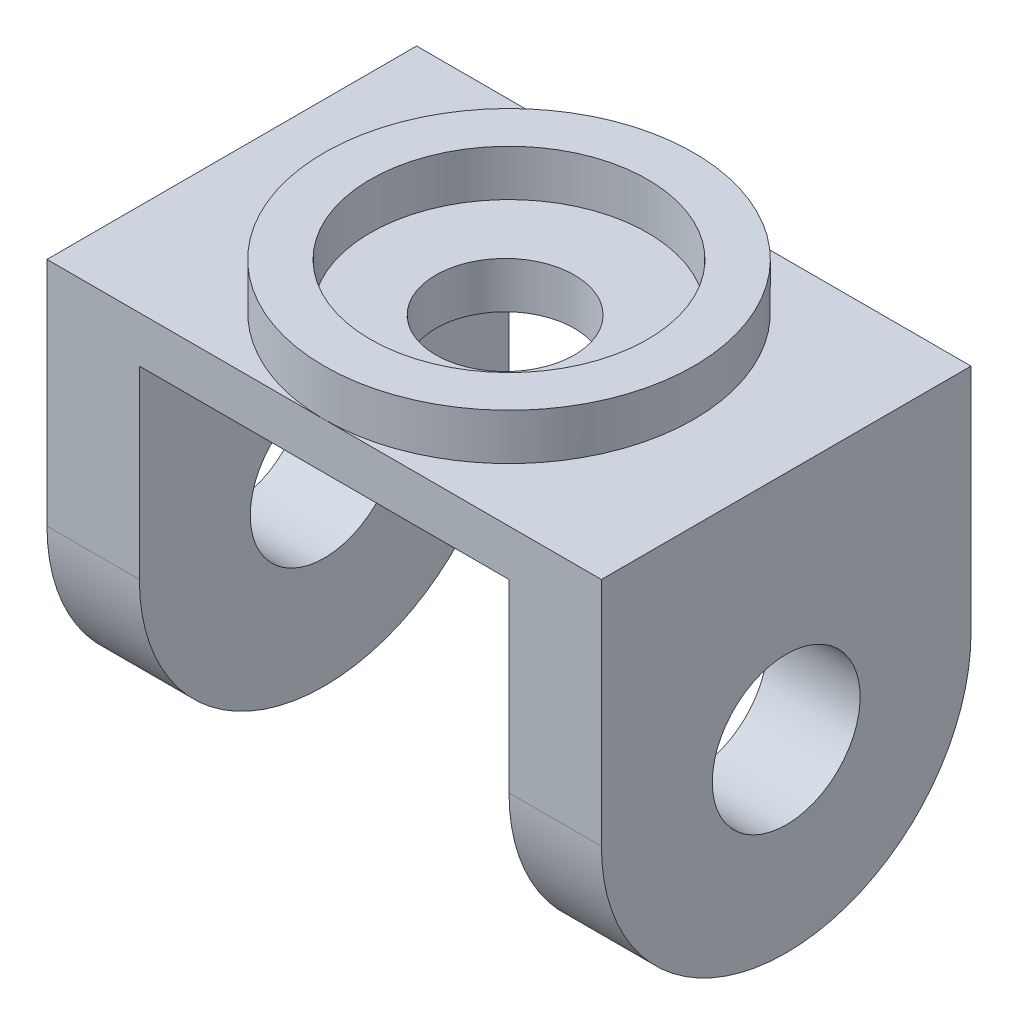
SolidWorks part; units mm, degrees
ref_plane "Front Plane" through (0, 0, 0) normal (0, 0, 1) x (1, 0, 0)
ref_plane "Top Plane" through (0, 0, 0) normal (0, 1, 0) x (1, 0, 0)
ref_plane "Right Plane" through (0, 0, 0) normal (1, 0, 0) x (0, 0, -1)
sketch "Sketch1" plane through (0, 0, 0) normal (0, 1, 0) x (1, 0, 0)
  line L1 (-60, 40) -> (60, 40)
  line L2 (-60, 40) -> (-60, -40)
  line L3 (-60, -40) -> (60, -40)
  line L4 (60, 40) -> (60, -40)
  line L5 (-60, 40) -> (60, -40) construction
  line L6 (-60, -40) -> (60, 40) construction
  point P0 (0, 0)
  dimension "D1" = 120
  dimension "D2" = 80
extrude "Boss-Extrude1" add sketch "Sketch1" along normal blind 10
sketch "Sketch2" plane through (0, 0, 0) normal (0, 1, 0) x (1, 0, 0)
  circle A0 centre (0, 0) radius 40
  circle A1 centre (0, 0) radius 30
extrude "Boss-Extrude2" add sketch "Sketch2" along normal blind 20
sketch "Sketch3" plane through (0, 10, 0) normal (0, 1, 0) x (1, 0, 0)
  circle A0 centre (0, -0.8405) radius 15
  dimension "D1" = 30
extrude "Cut-Extrude1" cut sketch "Sketch3" against normal blind 20
sketch "Sketch4" plane through (0, 0, 0) normal (0, -1, 0) x (1, 0, 0)
  line L0 (60, -40) -> (-60, -40) construction
  line L1 (-60, 40) -> (-40, 40)
  line L2 (-60, 40) -> (-60, -40)
  line L3 (-60, -40) -> (-40, -40)
  line L4 (-40, 40) -> (-40, -40)
  dimension "D1" = 20
extrude "Boss-Extrude3" add sketch "Sketch4" along normal blind 80
sketch "Sketch5" plane through (-60, 0, 0) normal (-1, 0, 0) x (0, 0, 1)
  circle A0 centre (0, -40) radius 16
fillet "Fillet1" 2 edges at (-50, -80, -40) (-50, -80, 40) type full round first side face at (-11.4286, -18.5714, -40) second side face at (-11.4286, -18.5714, 40) middle face at (-50, -80, 0)
extrude "Cut-Extrude3" cut sketch "Sketch5" against normal through all
mirror "Mirror5" about plane through (0, 0, 0) normal (1, 0, 0) of "Fillet1", "Boss-Extrude3"
mirror "Mirror6" about plane through (0, 0, 0) normal (1, 0, 0) of "Cut-Extrude3"
